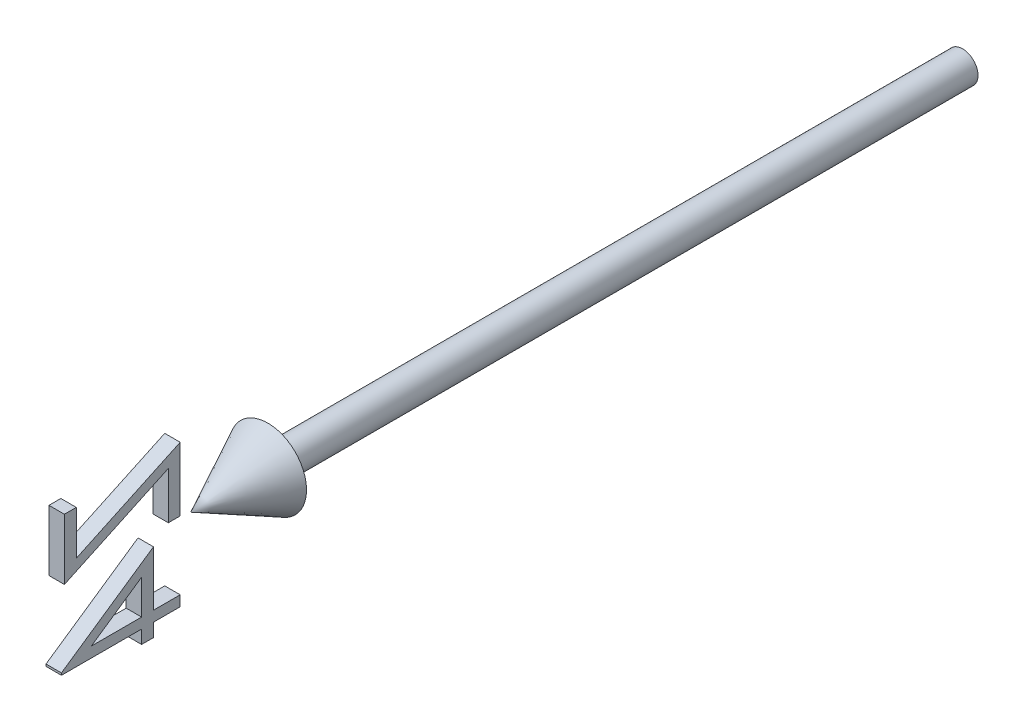
SolidWorks part; units mm, degrees
ref_plane "Front Plane" through (0, 0, 0) normal (0, 0, 1) x (1, 0, 0)
ref_plane "Top Plane" through (0, 0, 0) normal (0, 1, 0) x (1, 0, 0)
ref_plane "Right Plane" through (0, 0, 0) normal (1, 0, 0) x (0, 0, -1)
sketch "Sketch2" plane through (0, 0, 0) normal (0, 1, 0) x (1, 0, 0)
  line L0 (0, 41.95) -> (0, -114.4521) construction
  line L1 (-36.8894, 0) -> (41.4965, 0) construction
  line L2 (0, -100) -> (5, -90)
  line L3 (5, -90) -> (2, -90)
  line L4 (2, -90) -> (2, 0)
  line L5 (2, 0) -> (0, 0)
  line L6 (0, 0) -> (0, -100)
  dimension "D1" = 100
  dimension "D2" = 2
  dimension "D3" = 10
  dimension "D4" = 5
revolve "Revolve1" add sketch "Sketch2" angle 360 about L0
sketch "Sketch3" plane through (0, 0, 0) normal (1, 0, 0) x (0, -1, 0)
  line L0 (0, -101.5706) -> (0, -127.8138) construction
  line L1 (-10.1124, -102.3675) -> (14.1256, -102.3675) construction
  text T0 "Z4\r\n" font "Century Gothic" height 15
extrude "Boss-Extrude1" add sketch "Sketch3" against normal blind 1 and the other way blind 1 separate body
equation "\"frame_arrow_length\"=100"
equation "\"D1@Sketch2\"=\"frame_arrow_length\""
equation "\"frame_arrow_odA\"=4"
equation "\"D2@Sketch2\"=\"frame_arrow_odA\"/2"
equation "\"frame_arrow_head_od\"=5"
equation "\"D4@Sketch2\"=\"frame_arrow_head_od\""
equation "\"frame_arrow_head_length\"=10"
equation "\"D3@Sketch2\"=\"frame_arrow_head_length\""
equation "\"tvarobot_theta1\"=30"
equation "\"link0_ringA_odA\"= 40"
equation "\"link0_ringA_odB\"= 25"
equation "\"link0_ringA_id\"= 20"
equation "\"link0_ringA_thickness\"= (\"link0_ringA_odB\" - \"link0_ringA_id\")/2"
equation "\"link0_ringA_height\"= 3"
equation "\"link0_ringA_heightA\"= 1.5"
equation "\"link0_ringA_heightB\"=\"link0_ringA_height\"-\"link0_ringA_heightA\""
equation "\"link0_ringB_odA\"= 40"
equation "\"link0_ringB_odB\"= 29"
equation "\"link0_ringB_id\"= \"link0_shaftA_bearing_id\"+1"
equation "\"link0_ringB_thickness\"= (\"link0_ringB_odB\" - \"link0_ringB_id\")/2"
equation "\"link0_ringB_height\"= 3"
equation "\"link0_ringB_heightA\"= 1.5"
equation "\"link0_ringB_heightB\"=\"link0_ringB_height\"-\"link0_ringB_heightA\""
equation "\"link0_shaftA_bearing_od\"=27"
equation "\"link0_shaftA_bearing_id\"=20"
equation "\"link0_shaftA_thrust_bearing_od\"=35"
equation "\"link0_shaftA_thrust_bearing_id\"=20.04"
equation "\"link0_shaftA_retaining_ring_id\"=18.5"
equation "\"link0_shaftA_retaining_ring_groove_width\"=1.5"
equation "\"link0_shaftA_spline_length\"=8.0"
equation "\"link0_shaftA_spline_depth\"=1.0"
equation "\"link0_shaftA_spline_width\"=4.0"
equation "\"link0_shaftA_odA\"=\"link0_shaftA_bearing_id\""
equation "\"link0_shaftA_odB\"=35"
equation "\"link0_shaftA_odC\"=\"link0_shaftA_bearing_id\""
equation "\"link0_shaftA_odD\"=\"link0_shaftA_odC\"-2*\"link0_shaftA_spline_depth\""
equation "\"link0_shaftA_odE\"=\"link0_shaftA_bearing_id\""
equation "\"link0_shaftA_odF\"=\"link0_shaftA_odE\"-2*\"link0_shaftA_spline_depth\""
equation "\"link0_shaftA_idA\"=10"
equation "\"link0_shaftA_idB\"=6"
equation "\"link0_shaftA_length\"=39.5"
equation "\"link0_shaftA_lengthA\"=8.0"
equation "\"link0_shaftA_lengthB\"=12.0"
equation "\"link0_shaftA_lengthC\"=35.0"
equation "\"link0_shaftA_lengthD\"=39.0"
equation "\"link0_shaftA_lengthE\"=\"link0_shaftA_length\"-\"link0_shaftA_lengthD\""
equation "\"link0_shaftA_offsetX\"=11"
equation "\"link0_shaftA_offsetY\"=0"
equation "\"link0_shaftA_bolt_pattern_dia\"=14"
equation "\"link0_motor_center_dist\"=26"
equation "\"link0_46t_pulley_spline_length\"=8"
equation "\"link0_46t_pulley_spline_depth\"=\"link0_shaftA_spline_depth\"*1.025"
equation "\"link0_46t_pulley_spline_width\"=\"link0_shaftA_spline_width\"*1.05"
equation "\"link0_46t_pulley_idA\"=\"link0_shaftA_bearing_id\"*1.025"
equation "\"link0_46t_pulley_idB\"=\"link0_46t_pulley_idA\"-2*\"link0_46t_pulley_spline_depth\""
equation "\"link0_shaftB_spline_length\"=10"
equation "\"link0_shaftB_spline_depth\"=1.0"
equation "\"link0_shaftB_spline_width\"=1.25"
equation "\"link0_shaftB_length\"=7"
equation "\"link0_shaftB_lengthA\"=1.5"
equation "\"link0_shaftB_lengthB\"=2.75"
equation "\"link0_shaftB_odA\"=32"
equation "\"link0_shaftB_odB\"=22"
equation "\"link0_shaftB_odC\"=20"
equation "\"link0_shaftB_idA\"=10"
equation "\"link0_shaftB_bolt_diameter\"=19"
equation "\"link0_shaftB_bearing_od\"=27"
equation "\"link0_shaftB_bearing_id\"=20"
equation "\"link0_motor_length\"=46.5"
equation "\"link0_motor_width\"=28.5"
equation "\"link0_motor_height\"=34"
equation "\"link0_motor_offset\"=8"
equation "\"link0_shellA_thickness\"=2.5"
equation "\"link0_shellB_thickness\"=\"link0_shellA_thickness\""
equation "\"link0_plateA_shellA_height\"=48"
equation "\"link0_shellA_width\" =\"link0_plateA_width\""
equation "\"link0_shellA_height\" = \"link0_plateA_shellA_height\"-\"link0_plateA_height\""
equation "\"link0_shellA_length\" = \"link0_plateA_lengthB\" "
equation "\"link0_shellB_length\"=\"link0_shellA_length\""
equation "\"link0_shellA_radius\" = 0.375*25.4"
equation "\"link0_shellA_radiusA\"= \"link0_plateA_radiusA\""
equation "\"link0_shellA_radiusB\"= \"link0_plateA_radiusB\""
equation "\"link0_shellA_radiusC\"= 3"
equation "\"link0_postA_height\"=7"
equation "\"link0_postA_width\"=16"
equation "\"link0_postA_length\"=20"
equation "\"link0_postA_posX\"=22"
equation "\"link0_postA_posY\"=17.5"
equation "\"link0_postA_pocket_width\"=6.0"
equation "\"link0_postA_pocket_length\"=2.5"
equation "\"link0_postA_pocket_depth\"=9"
equation "\"link0_postA_pocket_posZ\"=10"
equation "\"link0_postB_height\"=7"
equation "\"link0_postB_width\"=16"
equation "\"link0_postB_length\"=20"
equation "\"link0_postB_posX\"=22"
equation "\"link0_postB_posY\"=17.5"
equation "\"link0_postB_id\"=3.0"
equation "\"link0_postB_pocket_width\"=6.0"
equation "\"link0_postB_pocket_length\"=2.5"
equation "\"link0_postB_pocket_depth\"=9"
equation "\"link0_postB_pocket_posZ\"=10"
equation "\"link0_postC_height\"=7"
equation "\"link0_postC_width\"=16"
equation "\"link0_postC_length\"=20"
equation "\"link0_postC_posX\"=22"
equation "\"link0_postC_posY\"=17.5"
equation "\"link0_postC_id\"=3.0"
equation "\"link0_postC_pocket_width\"=6.0"
equation "\"link0_postC_pocket_length\"=2.5"
equation "\"link0_postC_pocket_depth\"=9"
equation "\"link0_postC_pocket_posZ\"=10"
equation "\"link0_postD_height\"=7"
equation "\"link0_postD_width\"=16"
equation "\"link0_postD_length\"=20"
equation "\"link0_postD_posX\"=22"
equation "\"link0_postD_posY\"=17.5"
equation "\"link0_postD_id\"=3.0"
equation "\"link0_postD_pocket_width\"=6.0"
equation "\"link0_postD_pocket_length\"=3.0"
equation "\"link0_postD_pocket_depth\"=9"
equation "\"link0_postD_pocket_posZ\"=10"
equation "\"link0_postE_height\"=5"
equation "\"link0_postE_width\"=16"
equation "\"link0_postE_length\"=\"link0_plateE_lengthA\"-\"link0_lip_height\""
equation "\"link0_postE_posZ\"=22"
equation "\"link0_postE_posX\"=17.5"
equation "\"link0_postE_posY\"=22"
equation "\"link0_postE_id\"=3.0"
equation "\"link0_postE_cbore_id\"=6.5"
equation "\"link0_postE_hole_id\"=3"
equation "\"link0_postF_posZ\"=22"
equation "\"link0_postF_posX\"=17.5"
equation "\"link0_postF_posY\"=\"link0_plateB_lengthA\"+4"
equation "\"link0_postF_id\"=3.0"
equation "\"link0_postF_cbore_id\"=6.5"
equation "\"link0_postF_hole_id\"=3"
equation "\"link0_postG_posZ\"=22"
equation "\"link0_postG_posX\"=17.5"
equation "\"link0_postG_posY\"=\"link0_plateB_lengthA\"+12"
equation "\"link0_postG_id\"=3.0"
equation "\"link0_postG_cbore_id\"=6.5"
equation "\"link0_postG_hole_id\"=3"
equation "\"link0_postHIJ_posY\"=6"
equation "\"link0_postH_posX\"=28"
equation "\"link0_postH_posY\"=20"
equation "\"link0_postH_posZ\"=20"
equation "\"link0_postH_length\"=10"
equation "\"link0_postI_posX\"=28"
equation "\"link0_postI_posY\"=20"
equation "\"link0_postI_posZ\"=135"
equation "\"link0_postI_length\"=10"
equation "\"link0_postJ_posX\"=28"
equation "\"link0_postJ_posY\"=20"
equation "\"link0_postJ_posZ\"=175"
equation "\"link0_postJ_length\"=10"
equation "\"link0_postK_posX\"=28"
equation "\"link0_postK_posY\"=20"
equation "\"link0_postK_posZ\"=175"
equation "\"link0_postK_length\"=10"
equation "\"link0_postL_posX\"=28"
equation "\"link0_postL_posY\"=20"
equation "\"link0_postL_posZ\"=135"
equation "\"link0_postL_length\"=10"
equation "\"link0_postM_posX\"=28"
equation "\"link0_postM_posY\"=20"
equation "\"link0_postM_posZ\"=35"
equation "\"link0_postM_length\"=10"
equation "\"link0_plateA_lengthA\"=30"
equation "\"link0_plateA_lengthB\"=150"
equation "\"link0_plateA_lengthC\"=30"
equation "\"link0_plateA_length\"=\"link0_plateA_lengthA\"+\"link0_plateA_lengthB\"+\"link0_plateA_lengthC\""
equation "\"link0_plateA_width\"=  68"
equation "\"link0_plateA_height\"= \"link0_plateA_radiusA\""
equation "\"link0_plateA_thickness\"=\"link0_shellA_thickness\""
equation "\"link0_plateA_radius\"= 9.5"
equation "\"link0_plateA_radiusA\"= 18"
equation "\"link0_plateA_radiusB\"= 18"
equation "\"link0_plateA_radiusC\"= 3"
equation "\"link0_plateB_length\"= 40"
equation "\"link0_plateB_width\"= \"link0_plateA_width\"*1.005"
equation "\"link0_plateB_height\"= \"link0_plateA_shellA_height\"*1.005"
equation "\"link0_plateB_lengthA\"=\"link0_lip_height\"+\"link0_plateD_thickness\"+\"link0_motor_mount_thickness\""
equation "\"link0_plateB_lengthB\"=\"link0_plateB_height\"-\"link0_plateB_lengthA\""
equation "\"link0_plateB_radiusA\"= \"link0_plateA_radiusA\""
equation "\"link0_plateB_radiusB\"= \"link0_plateA_radiusB\""
equation "\"link0_plateB_radiusC\"= 3"
equation "\"link0_plateB_idA\"=\"link0_shaftA_odC\"+1"
equation "\"link0_plateB_idB\"=\"link0_shaftA_bearing_od\"-2"
equation "\"link0_plateB_idC\"=\"link0_shaftA_bearing_od\"*1.005"
equation "\"link0_plateB_idD\"=\"link0_shaftA_thrust_bearing_od\"+1 "
equation "\"link0_plateB_depthA\"=1.0"
equation "\"link0_plateB_depthB\"=2.0"
equation "\"link0_plateB_depthC\"=8"
equation "\"link0_plateB_depthD\"=\"link0_plateB_length\"-\"link0_lip_height\"-\"link0_plateD_thickness\" "
equation "\"link0_plateC_length\"=\"link0_plateB_length\""
equation "\"link0_plateC_width\"= \"link0_plateB_width\""
equation "\"link0_plateC_height\"= .1*25.4"
equation "\"link0_plateA_hole_od\" = 0.1*25.4"
equation "\"link0_plateA_hole_delx\" = 0.5*25.4"
equation "\"link0_plateA_hole_delz\" = 0.75*25.4"
equation "\"link0_plateA_hole_offx\" = 0.0*25.4"
equation "\"link0_plateA_hole_offz\" = \"link0_plateA_length\"/2"
equation "\"link0_plateB_hole_od\" = 0.1*25.4"
equation "\"link0_plateB_hole_delx\"= 0.75*25.4"
equation "\"link0_plateB_hole_delz\"= 0.75*25.4"
equation "\"link0_plateB_hole_offx\"= 0.0*25.4"
equation "\"link0_plateB_hole_offz\"= 0.0*25.4"
equation "\"link0_plateC_hole_od\"= 0.1*25.4"
equation "\"link0_plateC_hole_delx\"= 0.75*25.4"
equation "\"link0_plateC_hole_delz\"= 0.75*25.4"
equation "\"link0_plateC_hole_offx\"= 0.0*25.4"
equation "\"link0_plateC_hole_offz\"= 0.0*25.4"
equation "\"link0_plateD_height\"=\"link0_plateB_height\"-2*\"link0_shellA_thickness\""
equation "\"link0_plateD_width\"=\"link0_plateB_width\"-2*\"link0_shellA_thickness\""
equation "\"link0_plateD_thickness\"=10"
equation "\"link0_plateD_radiusA\"=\"link0_plateB_radiusA\"-\"link0_shellA_thickness\""
equation "\"link0_plateD_odA\"= .375*25.4"
equation "\"link0_plateD_odB\"= .375*25.4"
equation "\"link0_plateD_bearing_id\"=20"
equation "\"link0_plateD_bearing_od\"=27"
equation "\"link0_plateE_radiusA\"=\"link0_plateA_radiusA\""
equation "\"link0_plateE_radiusB\"=\"link0_plateA_radiusB\""
equation "\"link0_plateE_radiusC\"=8.0"
equation "\"link0_plateE_length\"=30"
equation "\"link0_plateE_lengthA\"=16"
equation "\"link0_plateE_height\"=\"link0_plateB_height\""
equation "\"link0_plateE_width\"=\"link0_plateB_width\""
equation "\"link0_plateE_odA\"=\"gantry_coupler_id\"*0.99"
equation "\"link0_plateE_idA\"=\"link0_plateE_odA\"-20.0"
equation "\"link0_plateE_spline_depth\"=\"link0_poleA_spline_depth\"*1.05"
equation "\"link0_plateE_spline_width\"=\"link0_poleA_spline_width\"*1.075"
equation "\"link0_plateE_spline_length\"=\"link0_poleA_spline_length\""
equation "\"link0_plateE_coupler_length\"=46"
equation "\"link0_lip_height\"=5.0"
equation "\"link0_lip_thickness\"=2.0"
equation "\"link0_motor_mount_thickness\"=8.0"
equation "\"link0_motor_mount_idA\"=22"
equation "\"link0_motor_mount_idB\"=\"link0_shaftB_bearing_od\"*1.005"
equation "\"link0_motor_mount_idC\"=\"link0_shaftB_bearing_od\"-2"
equation "\"link0_motor_mount_depthA\"=5.5"
equation "\"link0_motor_mount_height\"=\"link0_plateD_height\""
equation "\"link0_motor_mount_width\"=\"link0_plateD_width\""
equation "\"link0_motor_mountL_height\"=36"
equation "\"link0_motor_mountL_heightA\"=12"
equation "\"link0_motor_mountL_length\"=50"
equation "\"link0_motor_mountL_lengthA\"=36"
equation "\"gantry_coupler_od\"=25.4*2.0"
equation "\"gantry_coupler_id\"=1.645*25.4"
equation "\"gantry_coupler_offsetX\"=\"link0_plateE_width\"/2"
equation "\"link0_poleA_odA\"=20"
equation "\"link0_poleA_odB\"=36"
equation "\"link0_poleA_idA\"=\"link0_poleA_odA\"-2*\"link0_poleA_thickness\""
equation "\"link0_poleA_idB\"=(\"link0_plateE_idA\"/2+1.5*\"link0_lip_thickness\")*1.04"
equation "\"link0_poleA_thickness\"=3.5"
equation "\"link0_poleA_length\"=100"
equation "\"link0_poleA_lengthA\"=18.5"
equation "\"link0_poleA_lengthB\"=80"
equation "\"link0_poleA_gasket_thickness\"=1.5"
equation "\"link0_poleA_spline_depth\"=1.0"
equation "\"link0_poleA_spline_width\"=4.0"
equation "\"link0_poleA_spline_length\"=10.0"
equation "\"link1_plateB_length\"=30"
equation "\"link1_lip_height\"=\"link0_lip_height\""
equation "\"link0_tension_plateA_width\"=12"
equation "\"link0_tension_plateA_lengthA\"=10.5"
equation "\"link0_tension_plateB_width\"=\"link0_tension_plateA_width\""
equation "\"link0_tension_plateB_lengthA\"=\"link0_tension_plateA_lengthA\""
equation "\"link0_tension_wheelA_posZ\"=7"
equation "\"link0_tension_wheelA_posX\"=\"link0_plateD_height\"/2-\"link0_tension_plateA_lengthA\""
equation "\"link0_m2_clear_hole_id\"=2.35"
equation "\"link0_m2_insert_hole_id\"=2.5"
equation "\"link0_m2_tap_hole_id\"=1.75"
equation "\"link0_m2_nut_socket_width\"=4.25"
equation "\"link0_m2_nut_socket_depth\"=2.5"
equation "\"link0_m2_cbore_id\"=3.75"
equation "\"link0_m2_cbore_depth\"=7"
equation "\"link0_m2_5_clear_hole_id\"=2.75"
equation "\"link0_m2_5_insert_hole_id\"=2.75"
equation "\"link0_m2_5_tap_hole_id\"=2.25"
equation "\"link0_m2_5_nut_socket_width\"=5.25"
equation "\"link0_m2_5_nut_socket_depth\"=2.5"
equation "\"link0_m2_5_cbore_id\"=4.75"
equation "\"link0_m2_5_cbore_depth\"=2.5"
equation "\"link0_m2_5_insert_access_length\"=6.0"
equation "\"link0_m2_5_insert_access_width\"=3.0"
equation "\"link0_m3_clear_hole_id\"=3.25"
equation "\"link0_m3_insert_hole_id\"=3"
equation "\"link0_m3_tap_hole_id\"=2.75"
equation "\"link0_m3_nut_socket_width\"=5.75"
equation "\"link0_m3_nut_socket_depth\"=4.0"
equation "\"link0_m3_cbore_id\"=5.75"
equation "\"link0_m3_cbore_depth\"=3.5"
equation "\"link0_m3_insert_access_length\"=4.5"
equation "\"link0_m3_insert_access_width\"=3.5"
equation "\"link0_rpi_mount_height\"=6"
equation "\"link0_rpi_mount_width\"=49"
equation "\"link0_rpi_mount_length\"=58"
equation "\"link0_rpi_mount_post_od\"=6"
equation "\"link0_rpi_mount_posZ\"=72"
equation "\"link0_rpi_mount_posX\"=11.5"
equation "\"link0_mcu_mount_height\"=5"
equation "\"link0_mcu_mount_width\"=49"
equation "\"link0_mcu_mount_length\"=58"
equation "\"link0_mcu_mount_post_od\"=6"
equation "\"link0_mcu_mount_posZ\"=164"
equation "\"link0_mcu_mount_posX\"=4"
equation "\"link0_pwr_mount_height\"=4"
equation "\"link0_pwr_mount_width\"=15.75"
equation "\"link0_pwr_mount_length\"=75.75"
equation "\"link0_pwr_mount_post_od\"=6"
equation "\"link0_pwr_mount_posZ\"=75"
equation "\"link0_pwr_mount_posX\"=16"
equation "\"link0_pwr_board_height\"=6"
equation "\"link0_pwr_board_width\"=21"
equation "\"link0_pwr_board_length\"=80"
